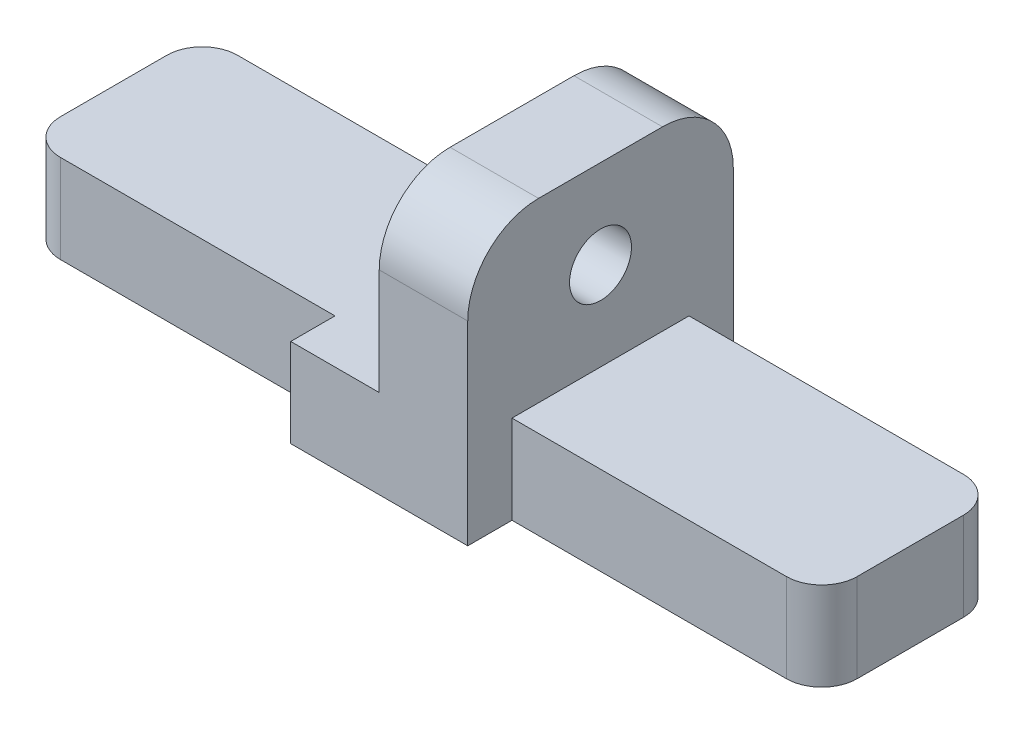
SolidWorks part; units mm, degrees
ref_plane "前视基准面" through (0, 0, 0) normal (0, 0, 1) x (1, 0, 0)
ref_plane "上视基准面" through (0, 0, 0) normal (0, 1, 0) x (1, 0, 0)
ref_plane "右视基准面" through (0, 0, 0) normal (1, 0, 0) x (0, 0, -1)
other "Configuration Table"
sketch "草图3" plane through (0, 0, 0) normal (0, 1, 0) x (1, 0, 0)
  line L1 (-22.5, 5) -> (22.5, 5)
  line L2 (-22.5, 5) -> (-22.5, -5)
  line L3 (-22.5, -5) -> (22.5, -5)
  line L4 (22.5, 5) -> (22.5, -5)
  line L5 (-22.5, 5) -> (22.5, -5) construction
  line L6 (-22.5, -5) -> (22.5, 5) construction
  point P0 (0, 0)
  dimension "D1" = 45
  dimension "D2" = 10
extrude "凸台-拉伸2" add sketch "草图3" along normal blind 5
sketch "草图4" plane through (0, 5, 0) normal (0, 1, 0) x (1, 0, 0)
  line L1 (-5, 7.5) -> (5, 7.5)
  line L2 (-5, 7.5) -> (-5, -7.5)
  line L3 (-5, -7.5) -> (5, -7.5)
  line L4 (5, 7.5) -> (5, -7.5)
  line L5 (-5, 7.5) -> (5, -7.5) construction
  line L6 (-5, -7.5) -> (5, 7.5) construction
  point P0 (0, 0)
  dimension "D1" = 10
  dimension "D2" = 15
extrude "凸台-拉伸3" add sketch "草图4" along normal blind 10 and the other way up to surface (5 mm away) other way up to face at (0, 0, 0)
sketch "草图5" plane through (-5, 0, 0) normal (-1, 0, 0) x (0, 0, 1)
  line L1 (0, 17.7731) -> (0, -1.9609) construction
  line L2 (-7.5, 10) -> (7.5, 10)
  line L3 (-7.5, 10) -> (7.5, 10) construction
  circle A0 centre (0, 10) radius 1.75
  dimension "D2" = 3.5
  dimension "D1" = 5
extrude "切除-拉伸1" cut sketch "草图5" against normal blind 10
sketch "草图8" plane through (-5, 0, 0) normal (-1, 0, 0) x (0, 0, 1)
  line L5 (-10, 15) -> (10, 15)
  line L6 (-10, 15) -> (-10, 5)
  line L7 (-10, 5) -> (10, 5)
  line L8 (10, 15) -> (10, 5)
  line L9 (-10, 15) -> (10, 5) construction
  line L10 (-10, 5) -> (10, 15) construction
  point P4 (0, 10)
  dimension "D1" = 10
  dimension "D2" = 20
extrude "切除-拉伸2" cut sketch "草图8" against normal blind 5
fillet "圆角2" radius 2 4 edges at (-22.5, 2.5, 5) (-22.5, 2.5, -5) (22.5, 2.5, -5) (22.5, 2.5, 5)
fillet "圆角1" radius 4 2 edges at (2.5, 15, 7.5) (2.5, 15, -7.5)
